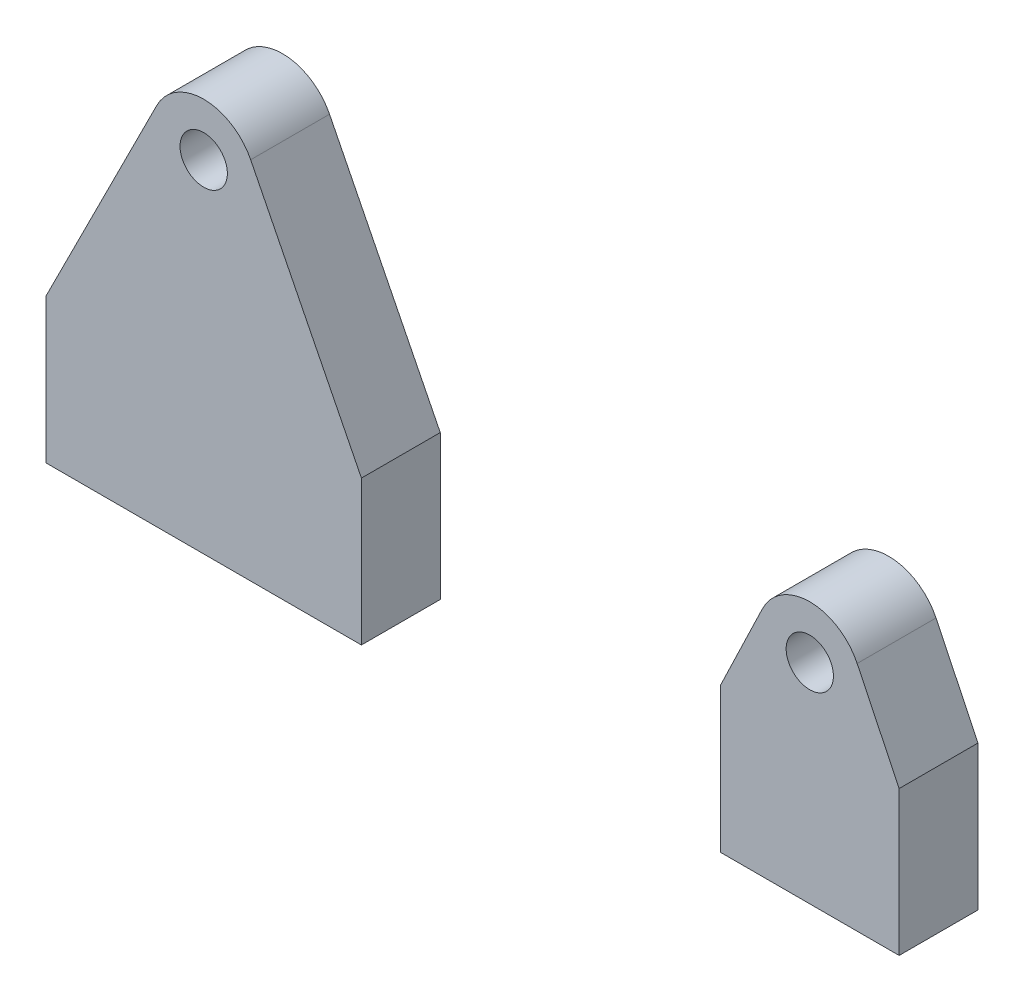
SolidWorks part; units mm, degrees
ref_plane "Front Plane" through (0, 0, 0) normal (0, 0, 1) x (1, 0, 0)
ref_plane "Top Plane" through (0, 0, 0) normal (0, 1, 0) x (1, 0, 0)
ref_plane "Right Plane" through (0, 0, 0) normal (1, 0, 0) x (0, 0, -1)
sketch "Sketch3" plane through (0, 0, -60) normal (0, 0, -1) x (-1, 0, 0)
  line L0 (432.0922, -538.8555) -> (439.9332, -543.2736) construction
  line L1 (546.9061, -514.9617) -> (555.6994, -516.8795) construction
  line L3 (745.1446, -583.3409) -> (146.7575, -583.3409) construction
  line L5 (745.1446, -553.3409) -> (146.7582, -553.3409) construction
  line L6 (745.1446, -553.3409) -> (146.7582, -553.3409)
  line L7 (745.1446, -583.3409) -> (146.7575, -583.3409)
  line L8 (560.2376, -511.4298) -> (581.3027, -553.3409)
  line L9 (542.3678, -511.4298) -> (521.3027, -553.3409)
  line L10 (551.3027, -515.9206) -> (551.3027, -553.3409) construction
  line L11 (436.0127, -541.0646) -> (436.0127, -553.3409) construction
  line L12 (427.0006, -536.7307) -> (419.0127, -553.3409)
  line L13 (445.0247, -536.7307) -> (453.0127, -553.3409)
  line L14 (581.3027, -553.3409) -> (581.3027, -583.3409)
  line L15 (739.316, -580.8409) -> (151.346, -580.8409) construction
  line L17 (521.3027, -583.3409) -> (521.3027, -553.3409)
  line L18 (453.0127, -553.3409) -> (453.0127, -580.8409)
  line L19 (453.0127, -580.8409) -> (419.0127, -580.8409)
  line L20 (419.0127, -580.8409) -> (419.0127, -553.3409)
  circle A0 centre (436.0127, -541.0646) radius 10
  circle A1 centre (551.3027, -515.9206) radius 10
  spline S0 degree 3 poles (555.6994, -514.9617) (553.7816, -506.1684) (544.9883, -508.0862) (546.9061, -516.8795) (548.8238, -525.6728) (557.6171, -523.755) (555.6994, -514.9617) (553.7816, -506.1684) (544.9883, -508.0862) knots -0.5 0 0 0 0.5 0.5 0.5 1 1 1 1.5 1.5 1.5 weights 1 0.333333 0.333333 1 0.333333 0.333333 1 0.333333 0.333333 only from (555.6994, -514.9617) to (555.6994, -514.9617) construction
  spline S1 degree 3 poles (440.4093, -540.1057) (438.4916, -531.3124) (429.6983, -533.2301) (431.616, -542.0235) (433.5338, -550.8168) (442.3271, -548.899) (440.4093, -540.1057) (438.4916, -531.3124) (429.6983, -533.2301) knots -0.5 0 0 0 0.5 0.5 0.5 1 1 1 1.5 1.5 1.5 weights 1 0.333333 0.333333 1 0.333333 0.333333 1 0.333333 0.333333 only from (440.4093, -540.1057) to (440.4093, -540.1057) construction
  spline S2 degree 3 poles (555.6994, -514.9617) (553.7816, -506.1684) (544.9883, -508.0862) (546.9061, -516.8795) (548.8238, -525.6728) (557.6171, -523.755) (555.6994, -514.9617) (553.7816, -506.1684) (544.9883, -508.0862) knots -0.5 0 0 0 0.5 0.5 0.5 1 1 1 1.5 1.5 1.5 weights 1 0.333333 0.333333 1 0.333333 0.333333 1 0.333333 0.333333 only from (555.6994, -514.9617) to (555.6994, -514.9617)
  spline S3 degree 3 poles (440.4093, -540.1057) (438.4916, -531.3124) (429.6983, -533.2301) (431.616, -542.0235) (433.5338, -550.8168) (442.3271, -548.899) (440.4093, -540.1057) (438.4916, -531.3124) (429.6983, -533.2301) knots -0.5 0 0 0 0.5 0.5 0.5 1 1 1 1.5 1.5 1.5 weights 1 0.333333 0.333333 1 0.333333 0.333333 1 0.333333 0.333333 only from (440.4093, -540.1057) to (440.4093, -540.1057)
  spline S4 degree 3 poles (440.4093, -540.1057) (438.4916, -531.3124) (429.6983, -533.2301) (431.616, -542.0235) (433.5338, -550.8168) (442.3271, -548.899) (440.4093, -540.1057) (438.4916, -531.3124) (429.6983, -533.2301) knots -0.5 0 0 0 0.5 0.5 0.5 1 1 1 1.5 1.5 1.5 weights 1 0.333333 0.333333 1 0.333333 0.333333 1 0.333333 0.333333 only from (440.4093, -540.1057) to (440.4093, -540.1057)
  line M3 (739.3144, -555.8409) -> (151.3464, -555.8409)
  line M5 (151.346, -580.8409) -> (739.316, -580.8409)
  dimension "D1" = 20
  dimension "D2" = 20
  dimension "D3" = 30
  dimension "D4" = 30
  dimension "D5" = 17
  dimension "D6" = 17
extrude "Boss-Extrude1" add sketch "Sketch3" along normal blind 15 contours A1 L9 L6 L8 | A1 S2 | A0 S3 | A0 L12 L6 L13 | L20 L18 L6 M3 | L20 L18 M5 M3 | L17 L14 L6 M3 | L17 L14 M5 M3 region at (-551.3027, -554.5909, -60) region at (-551.3027, -539.3774, -60) region at (-560.7576, -513.6782, -60) region at (-551.3027, -568.3409, -60) region at (-436.0127, -554.5909, -60) region at (-436.0127, -552.9625, -60) region at (-445.4868, -538.9049, -60) region at (-436.0127, -568.3409, -60)
